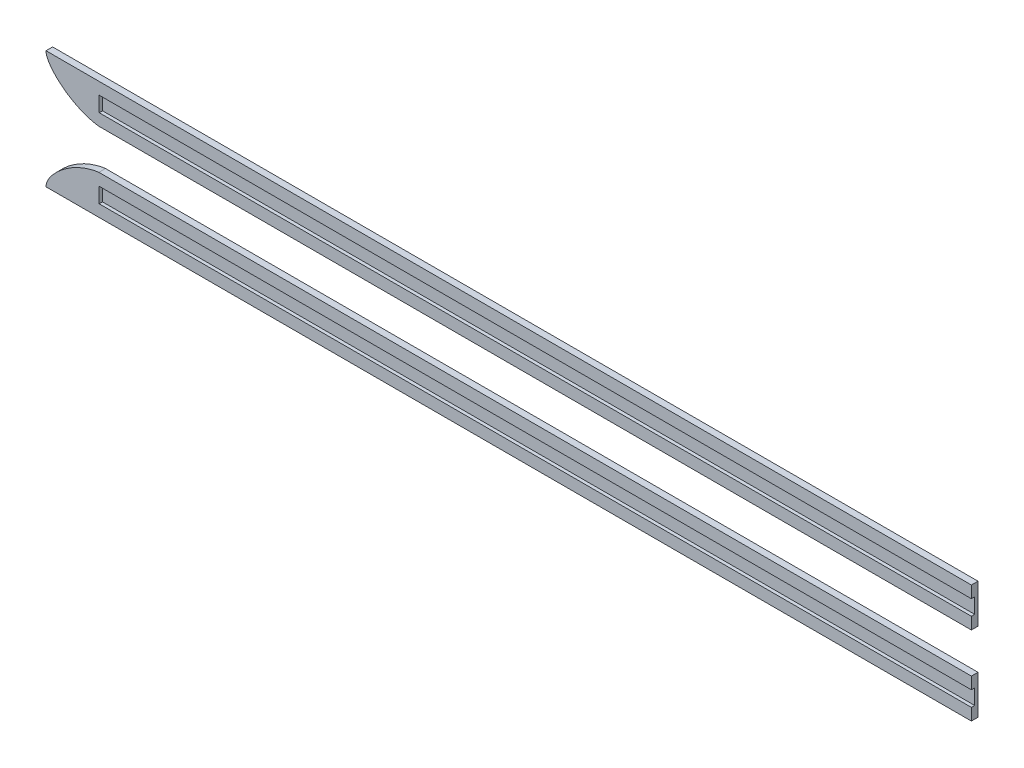
SolidWorks part; units mm, degrees
ref_plane "前视基准面" through (0, 0, 0) normal (0, 0, 1) x (1, 0, 0)
ref_plane "上视基准面" through (0, 0, 0) normal (0, 1, 0) x (1, 0, 0)
ref_plane "右视基准面" through (0, 0, 0) normal (1, 0, 0) x (0, 0, -1)
sketch "草图2" plane through (0, 0, 0) normal (0, 0, 1) x (1, 0, 0)
  line L1 (-82.8965, 44.5806) -> (617.1035, 44.5806)
  line L3 (-42.893, 15.0885) -> (617.1035, 15.0885)
  line L4 (617.1035, 44.5806) -> (617.1035, 15.0885)
  spline S0 degree 3 poles (-82.8965, 44.5806) (-83.0952, 35.7674) (-64.1582, 17.7514) (-42.893, 15.0885) knots 0 0 0 0 1 1 1 1
  point P4 (0, 0)
  point P5 (-43.7532, 14.5806)
  point P7 (-45.8955, 15.0885)
  point P8 (-43.7532, 15.0885)
  point P9 (0, 0)
  point P10 (0, 0)
  point P11 (0, 0)
  point P12 (0, 0)
  point P13 (0, 0)
  point P14 (0, 0)
extrude "凸台-拉伸1" add sketch "草图2" along normal blind 5 contours L3 L4 L1 S0
sketch "草图3" plane through (0, 0, 5) normal (0, 0, 1) x (1, 0, 0)
  line L1 (-42.6194, 35.5806) -> (617.3806, 35.5806)
  line L2 (-42.6194, 35.5806) -> (-42.6194, 24.0885)
  line L3 (-42.6194, 24.0885) -> (617.3806, 24.0885)
  line L4 (617.3806, 35.5806) -> (617.3806, 24.0885)
  line L6 (-82.8965, 44.5806) -> (617.1035, 44.5806) construction
  line L7 (-42.893, 15.0885) -> (617.1035, 15.0885) construction
  point P4 (0, 0)
  dimension "D1" = 9
  dimension "D2" = 9
extrude "切除-拉伸1" cut sketch "草图3" against normal blind 2.5 contours L2 L1 L4 L3
mirror "镜向9" about plane through (0, 0, 0) normal (0, 1, 0) of bodies 102
